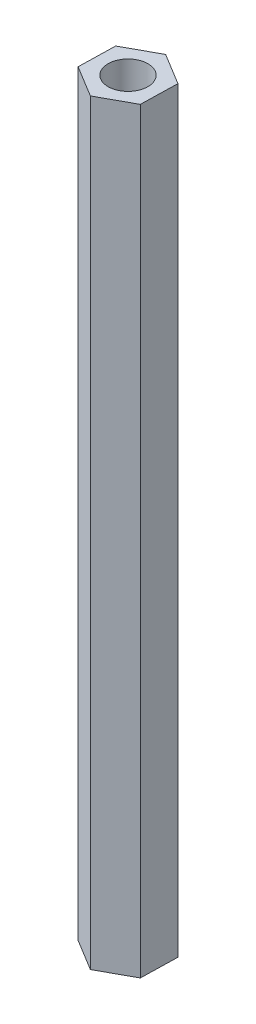
SolidWorks part; units mm, degrees
note: The reader was unsure of these and kept them because the rebuilt part matched: shared geometry of "Sketch1<3>", "Sketch1<4>".
material "AISI 316 Annealed Stainless Steel Bar (SS)"
ref_plane "Front Plane" through (0, 0, 0) normal (0, 0, 1) x (1, 0, 0)
ref_plane "Top Plane" through (0, 0, 0) normal (0, 1, 0) x (1, 0, 0)
ref_plane "Right Plane" through (0, 0, 0) normal (1, 0, 0) x (0, 0, -1)
sketch "Sketch1" plane through (0, 0, 0) normal (0, 1, 0) x (1, 0, 0)
  line L1 (4.0521, 2.2167) -> (0.1063, 4.6176)
  line L2 (0.1063, 4.6176) -> (-3.9458, 2.4008)
  line L3 (-3.9458, 2.4008) -> (-4.0521, -2.2167)
  line L4 (-4.0521, -2.2167) -> (-0.1063, -4.6176)
  line L5 (-0.1063, -4.6176) -> (3.9458, -2.4008)
  line L6 (3.9458, -2.4008) -> (4.0521, 2.2167)
  circle A0 centre (0, 0) radius 4 construction
  circle A1 centre (0, 0) radius 2.5
  dimension "D2" = 5
  dimension "D1" = 8
extrude "Boss-Extrude1" add sketch "Sketch1" along normal mid plane 95 contours L1 L2 L3 L4 L5 L6
extrude "Cut-Extrude1" cut sketch "Sketch1<3>" against normal blind 14 from offset 48 contours A1
sketch "Sketch1<3>" plane through (0, 0, 0) normal (0, 1, 0) x (1, 0, 0) same geometry as "Sketch1"
extrude "Cut-Extrude2" cut sketch "Sketch1<4>" along normal blind 14 from offset 48 contours A1
sketch "Sketch1<4>" plane through (0, 0, 0) normal (0, 1, 0) x (1, 0, 0) same geometry as "Sketch1"
